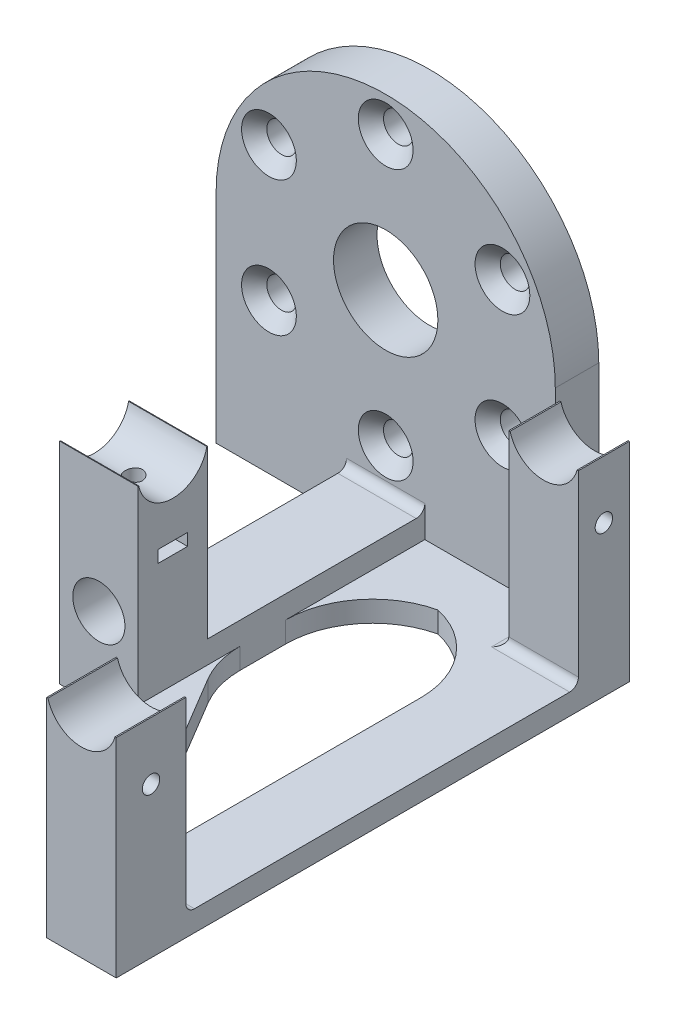
SolidWorks part; units mm, degrees
ref_plane "Front Plane" through (0, 0, 0) normal (0, 0, 1) x (1, 0, 0)
ref_plane "Top Plane" through (0, 0, 0) normal (0, 1, 0) x (1, 0, 0)
ref_plane "Right Plane" through (0, 0, 0) normal (1, 0, 0) x (0, 0, -1)
sketch "Sketch5" plane through (0, 0, 0) normal (0, 0, 1) x (1, 0, 0)
  line L0 (0, 0) -> (0, 15.5) construction
  circle A0 centre (0, 0) radius 19.5
  circle A1 centre (0, 15.5) radius 1.5
  circle A2 centre (0, 0) radius 6
  circle A3 centre (13.4234, 7.75) radius 1.5
  circle A4 centre (13.4234, -7.75) radius 1.5
  circle A5 centre (0, -15.5) radius 1.5
  circle A6 centre (-13.4234, -7.75) radius 1.5
  circle A7 centre (-13.4234, 7.75) radius 1.5
  point P18 (0, 0)
  dimension "D2" = 3
  dimension "D3" = 39
  dimension "D4" = 12
  dimension "D1" = 15.5
  dimension "D5" = 6
extrude "Boss-Extrude1" add sketch "Sketch5" along normal blind 5
hole_wizard "CSK for M3 Flat Head Machine Screw1" positions "Sketch7" profile "Sketch6" countersink size "M3" standard "ANSI Metric" end condition through all
sketch "Sketch7" plane through (0, 0, 5) normal (0, 0, 1) x (1, 0, 0)
  point P0 (-13.4234, 7.75)
  point P3 (0, 15.5)
  point P6 (13.4234, 7.75)
  point P9 (13.4234, -7.75)
  point P12 (0, -15.5)
  point P15 (-13.4234, -7.75)
sketch "Sketch6" plane through (-13.4234, 7.75, 5) normal (1, 0, 0) x (0, -1, 0)
  line L0 (0, 0) -> (0, 5)
  line L1 (0, 5) -> (1.7, 5)
  line L2 (1.7, 5) -> (1.7, 1.45)
  line L3 (1.7, 1.45) -> (3.15, 0)
  line L5 (3.15, 0) -> (0, 0)
  line L6 (-1.7, 1.45) -> (-3.15, 0) construction
  line L11 (0, -6.35) -> (0, 107.95) construction
  dimension "Thru Hole Dia." = 3.4
  dimension "Thru Hole Depth" = 5
  dimension "Near C'Sink Dia." = 6.3
  dimension "Near C'Sink Angle" = 90
sketch "Sketch8" plane through (0, 0, 5) normal (0, 0, 1) x (1, 0, 0)
  line L0 (-19.5, 0) -> (-19.5, -25)
  line L1 (-19.5, -25) -> (19.5, -25)
  line L2 (19.5, -25) -> (19.5, 0)
  circle A0 centre (0, 0) radius 19.5 construction
  arc A1 (-19.5, 0) -> (19.5, 0) centre (0, 0) ccw
  dimension "D1" = 25
extrude "Boss-Extrude2" add sketch "Sketch8" against normal up to surface (5 mm away) up to face at (-11.7234, 7.75, 0)
sketch "Sketch9" plane through (0, 0, 5) normal (0, 0, 1) x (1, 0, 0)
  line L0 (-19.5, -25) -> (19.5, -25) construction
  line L4 (-4.5, -20) -> (-4.5, -25)
  line L5 (4.5, -20) -> (-4.5, -25) construction
  line L6 (4.5, -25) -> (-4.5, -20) construction
  line L7 (-19.5, -25) -> (0, -22.5) construction
  line L8 (0, -22.5) -> (19.5, -25) construction
  line L9 (-4.5, -25) -> (4.5, -25)
  line L10 (-4.5, -20) -> (4.5, -20)
  line L11 (4.5, -20) -> (4.5, -25)
  point P0 (0, -22.5)
  dimension "D1" = 5
  dimension "D2" = 9
extrude "Boss-Extrude3" add sketch "Sketch9" along normal blind 32.9817
sketch "Sketch10" plane through (0.3712, -20, 0) normal (0, 1, 0) x (1, 0, 0)
  line L1 (-4.8712, -37.9817) -> (4.1288, -37.9817)
  line L2 (-4.8712, -37.9817) -> (-4.8712, -29.9817)
  line L3 (-4.8712, -29.9817) -> (4.1288, -29.9817)
  line L4 (4.1288, -37.9817) -> (4.1288, -29.9817)
  line L6 (-4.8712, -37.9817) -> (-4.8712, -5) construction
  line L7 (4.1288, -37.9817) -> (4.1288, -5) construction
  point P7 (0, 0)
  point P8 (0, 0)
  point P11 (0, 0)
  dimension "D1" = 8
extrude "Boss-Extrude4" add sketch "Sketch10" along normal blind 24
sketch "Sketch11" plane through (-4.5, 0, 0) normal (-1, 0, 0) x (0, 0, 1)
  line L0 (29.9817, 4) -> (29.9817, -20) construction
  line L2 (29.9817, 4) -> (37.9817, 4) construction
  line L3 (37.9817, 4) -> (37.9817, -25) construction
  line L4 (29.9817, 0) -> (27.1369, 2.0822)
  line L5 (27.1369, 2.0822) -> (27.3574, 4.8482)
  line L6 (27.3574, 4.8482) -> (32.7492, 5.4696)
  line L7 (32.7492, 5.4696) -> (41.4483, 5.0286)
  line L8 (41.4483, 5.0286) -> (40.8237, 2.383)
  line L9 (40.8237, 2.383) -> (37.9817, 0)
  line L10 (29.9817, -0.8) -> (30.0625, -0.8)
  line L11 (37.9009, -0.8) -> (37.9817, -0.8)
  line L12 (37.9817, 0) -> (37.9817, -0.8)
  line L13 (29.9817, -0.8) -> (29.9817, 0)
  arc A0 (30.0625, -0.8) -> (37.9009, -0.8) centre (33.9817, 0) ccw
  dimension "D1" = 0.8
extrude "Cut-Extrude1" cut sketch "Sketch11" against normal blind 20
sketch "Sketch12" plane through (0, -0.8, 0) normal (0, 1, 0) x (1, 0, 0)
  line L0 (-4.5, -29.9817) -> (4.5, -37.9817) construction
  line L1 (4.5, -29.9817) -> (-4.5, -37.9817) construction
  line L2 (4.5, -37.9009) -> (4.5, -30.0625) construction
  line L3 (4.5, -29.9817) -> (4.5, -5) construction
  circle A0 centre (0, -33.9817) radius 1
  point P10 (0, 0)
  point P11 (0, 0)
  point P14 (0, 0)
  point P15 (0, 0)
  dimension "D1" = 2
extrude "Cut-Extrude2" cut sketch "Sketch12" against normal blind 16
sketch "Sketch13" plane through (-4.5, 0, 0) normal (-1, 0, 0) x (0, 0, 1)
  line L0 (29.9817, -8.9707) -> (32.2817, -8.9707) construction
  line L1 (32.2817, -8.2443) -> (35.6817, -8.2443)
  line L2 (32.2817, -8.2443) -> (32.2817, -9.6366)
  line L3 (32.2817, -9.6366) -> (35.6817, -9.6366)
  line L4 (35.6817, -8.2443) -> (35.6817, -9.6366)
  line L5 (29.9817, -0.8) -> (29.9817, -20) construction
  line L6 (37.9817, -0.8) -> (37.9817, -25) construction
  line L7 (35.6817, -8.9707) -> (37.9817, -8.9707) construction
  dimension "D1" = 3.4
extrude "Cut-Extrude3" cut sketch "Sketch13" against normal up to surface (9 mm away) up to face at (4.5, -12.05, 26.7363)
sketch "Sketch14" plane through (0, -25, 0) normal (0, -1, 0) x (1, 0, 0)
  line L0 (4.5, 37.9817) -> (4.5, 5) construction
  line L1 (4.5, 5) -> (28.015, 5)
  line L2 (4.5, 5) -> (4.5, 11)
  line L3 (4.5, 11) -> (20.015, 11)
  line L4 (28.015, 5) -> (28.015, 12.4921)
  line L5 (28.015, -8.3073) -> (28.015, 26.1777) construction
  line L6 (20.015, 73.6627) -> (20.015, 39.1777) construction
  line L8 (28.015, 12.4921) -> (28.015, 64)
  line L9 (28.015, 64) -> (20.015, 64)
  line L10 (20.015, 11) -> (20.015, 64)
  line L12 (4.5, 5) -> (19.5, 5) construction
  dimension "D1" = 0
  dimension "D2" = 6
  dimension "D3" = 59
extrude "Boss-Extrude5" add sketch "Sketch14" against normal blind 2.4
sketch "Sketch15" plane through (28.015, 0, 0) normal (1, 0, 0) x (0, 0, -1)
  line L0 (-42.1777, 4) -> (-73.6627, 4) construction
  line L1 (-64, -22.6) -> (-56, -22.6)
  line L2 (-64, -22.6) -> (-64, 4)
  line L3 (-64, 4) -> (-56, 4)
  line L4 (-56, -22.6) -> (-56, 4)
  line L6 (-5, -22.6) -> (-13, -22.6)
  line L7 (-5, -22.6) -> (-5, 4)
  line L8 (-5, 4) -> (-13, 4)
  line L9 (-13, -22.6) -> (-13, 4)
  point P14 (0, 0)
  point P15 (0, 0)
  point P16 (0, 0)
  dimension "D1" = 8
extrude "Boss-Extrude6" add sketch "Sketch15" against normal up to surface (8 mm away) up to face at (20.015, -23.8, 37.5)
sketch "Sketch16" plane through (0, 0, 64) normal (0, 0, 1) x (1, 0, 0)
  line L0 (20.015, -1.0579) -> (20.1574, -1.0579)
  line L1 (20.015, 4) -> (20.015, -25) construction
  line L2 (28.015, 4) -> (28.015, -25) construction
  line L3 (28.015, -1.0579) -> (30.9797, 0.9089)
  line L4 (30.9797, 0.9089) -> (30.0419, 7.8056)
  line L5 (20.015, -1.0579) -> (20.015, 10.6199)
  line L6 (20.015, 5.7446) -> (20.015, 15.4952) construction
  line L7 (20.015, 10.6199) -> (30.0419, 7.8056)
  line L8 (27.8726, -1.0579) -> (28.015, -1.0579)
  arc A0 (20.1574, -1.0579) -> (27.8726, -1.0579) centre (24.015, 0) ccw
extrude "Cut-Extrude4" cut sketch "Sketch16" against normal up to surface (59 mm away) up to face at (22.51, -14.5333, 5)
sketch "Sketch17" plane through (0, -22.6, 0) normal (0, 1, 0) x (1, 0, 0)
  line L0 (20.015, -56) -> (20.015, -13) construction
  line L1 (20.015, -13.8581) -> (28.015, -13.8581)
  line L2 (20.015, -13.8581) -> (20.015, -10.8581)
  line L3 (20.015, -10.8581) -> (28.015, -10.8581)
  line L4 (28.015, -13.8581) -> (28.015, -10.8581)
  line L5 (28.015, -5) -> (28.015, -13) construction
  dimension "D1" = 3
extrude "Cut-Extrude5" cut sketch "Sketch17" along normal up to surface (21.5421 mm away) up to face at (20.0862, -1.0579, 9)
sketch "Sketch19" plane through (0, 0, 29.9817) normal (0, 0, -1) x (-1, 0, 0)
  circle A0 centre (0, -15.5) radius 3
  dimension "D1" = 6
extrude "Cut-Extrude6" cut sketch "Sketch19" against normal through all
sketch "Sketch20" plane through (0, -22.6, 0) normal (0, 1, 0) x (1, 0, 0)
  line L0 (20.015, -64) -> (4.5, -37.9817)
  line L1 (20.015, -55) -> (4.5, -28.9817)
  line L2 (20.015, -56) -> (20.015, -11) construction
  line L3 (4.5, -29.9817) -> (4.5, -5) construction
  line L4 (4.5, -28.9817) -> (4.5, -37.9817)
  line L5 (20.015, -55) -> (20.015, -64)
  dimension "D1" = 9
extrude "Boss-Extrude7" add sketch "Sketch20" against normal up to surface (2.4 mm away) up to face at (8.005, -25, 20.4969)
fillet "Fillet1" radius 10 3 edges at (20.015, -23.8, 11) (4.5, -23.8, 11) (4.5, -23.8, 28.9817)
fillet "Fillet2" radius 1 1 edges at (20.015, -23.8, 55)
fillet "Fillet3" radius 1 5 edges at (0, -20, 5) (20.015, -22.6, 60) (20.015, -22.6, 7.9291) (24.015, -22.6, 10.8581) (24.015, -22.6, 56)
sketch "Sketch22" plane through (28.015, 0, 0) normal (1, 0, 0) x (0, 0, -1)
  circle A0 centre (-60, -7.7015) radius 1
extrude "Cut-Extrude7" cut sketch "Sketch22" against normal up to surface (8 mm away) up to face at (20.015, -11.329, 60)
sketch "Sketch23" plane through (28.015, 0, 0) normal (1, 0, 0) x (0, 0, -1)
  circle A0 centre (-7.9291, -7.7015) radius 1
extrude "Cut-Extrude8" cut sketch "Sketch23" against normal up to surface (8 mm away) up to face at (20.015, -11.329, 7.9291)
